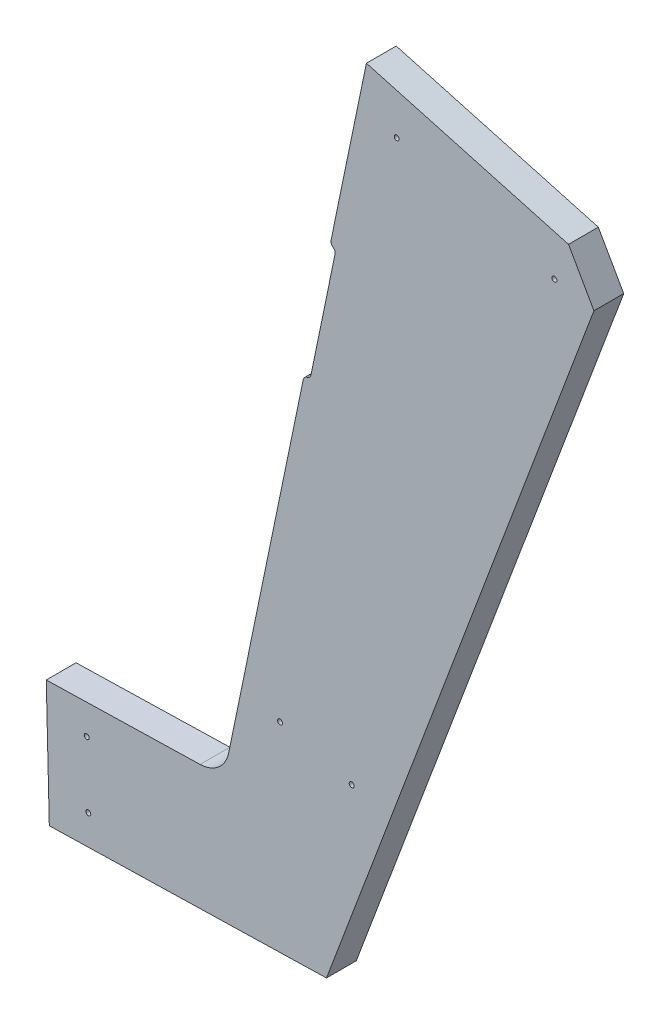
SolidWorks part; units mm, degrees
material "Beech"
ref_plane "Front Plane" through (0, 0, 0) normal (0, 0, 1) x (1, 0, 0)
ref_plane "Top Plane" through (0, 0, 0) normal (0, 1, 0) x (1, 0, 0)
ref_plane "Right Plane" through (0, 0, 0) normal (1, 0, 0) x (0, 0, -1)
sketch "Sketch1" plane through (0, 0, 0) normal (0, 0, 1) x (1, 0, 0)
  line L0 (-61.7531, -505.1337) -> (-59.8053, -584.9036)
  line L1 (-70.6552, -530.7587) -> (-61.1331, -530.5262) construction
  line L12 (272.1416, -96.993) -> (142.9339, -61.3062)
  line L13 (142.9339, -61.3062) -> (54.7807, -487.5464)
  line L14 (36.5905, -502.7325) -> (-61.7531, -505.1337)
  line L16 (-59.8053, -584.9036) -> (117.3871, -580.5771)
  line L17 (117.3871, -580.5771) -> (288.3946, -125.6501)
  line L37 (288.3946, -125.6501) -> (272.1416, -96.993)
  arc A0 (54.7807, -487.5464) -> (36.5905, -502.7325) centre (36.1255, -483.6882) cw
  dimension "D2" = 19.05
  dimension "D1" = 112
  dimension "D3" = 9.525
  dimension "D4" = 79.7937
  dimension "D5" = 435.6771
  dimension "D6" = 84.839
extrude "Boss-Extrude1" add sketch "Sketch1" along normal blind 19.05
hole_wizard "Hole2" positions "Sketch4" profile "Sketch5" legacy
sketch "Sketch4" plane through (295.8209, -105.8941, -19.05) normal (0, 0, -1) x (-0.3519, -0.9361, 0)
  line L0 (9.7688, 133.4475) -> (528.1685, 52.1167) construction
  line L5 (0.0093, 25.4) -> (517.3743, 25.4) construction
  line L8 (660.1216, 540.8653) -> (441.5979, 0) construction
  line L11 (698.7793, 525.2466) -> (486.5659, 0) construction
  line L15 (604.5365, 403.2872) -> (643.1942, 387.6685) construction
  line L17 (520.7568, 195.9254) -> (559.4145, 180.3066) construction
  line L19 (507.6737, 163.5435) -> (546.3314, 147.9247) construction
  point P17 (34.8618, 129.5107)
  point P19 (398.7112, 72.427)
  point P22 (25.4093, 25.4)
  point P24 (393.7093, 25.4)
  point P40 (604.5365, 403.2872)
  point P41 (643.1942, 387.6685)
  point P44 (520.7568, 195.9254)
  point P45 (559.4145, 180.3066)
  point P48 (507.6737, 163.5435)
  point P49 (546.3314, 147.9247)
sketch "Sketch5" plane through (-34.8779, -565.2393, -19.05) normal (1, 0, 0) x (0, 1, 0)
  line L0 (0, 0) -> (0, 40.64)
  line L1 (0, 40.64) -> (1.5875, 39.6861)
  line L2 (1.5875, 39.6861) -> (1.5875, 4.0177)
  line L3 (1.5875, 4.0177) -> (5.08, 0)
  line L4 (5.08, 0) -> (0, 0)
  line L5 (0, -14.3089) -> (0, 102.4216) construction
  line L6 (0, 40.64) -> (-1.5875, 39.6861) construction
  line L7 (-1.5875, 4.0177) -> (-5.08, 0) construction
  dimension "Diameter" = 3.175
  dimension "Depth" = 40.64
  dimension "C-Sink Diameter" = 10.16
  dimension "C-Sink Angle" = 82
  dimension "Drill Angle" = 118
sketch "Sketch6" plane through (149.23, -30.8631, 0) normal (-0.9793, 0.2025, 0) x (0, 0, 1)
  line L0 (19.05, -31.0873) -> (19.05, -466.3478) construction
  line L1 (19.05, -145.3873) -> (0, -145.3873)
  line L2 (19.05, -145.3873) -> (19.05, -227.9373)
  line L3 (19.05, -227.9373) -> (0, -227.9373)
  line L4 (0, -145.3873) -> (0, -227.9373)
  line L5 (0, -31.0873) -> (0, -466.3478) construction
  line L6 (19.05, -31.0873) -> (0, -31.0873) construction
  dimension "D1" = 114.3
  dimension "D2" = 82.55
extrude "Cut-Extrude1" cut sketch "Sketch6" against normal blind 3.81
fillet "Fillet1" radius 3.175 2 edges at (106.797, -254.8484, 9.525) (123.5158, -174.0091, 9.525)
fillet "Fillet2" radius 3.175 2 edges at (119.7847, -173.2375, 9.525) (103.0659, -254.0767, 9.525)
hole_wizard "15/64 (0.23438) Diameter Hole1" positions "Sketch7" profile "Sketch8" hole size "15/64" standard "ANSI Inch"
sketch "Sketch7" plane through (152.9611, -31.6348, 0) normal (-0.9793, 0.2025, 0) x (0, 0, 1)
  point P0 (9.525, -186.6623)
sketch "Sketch8" plane through (115.1564, -214.4287, 9.525) normal (0, 0, 1) x (-0.2025, -0.9793, 0)
  line L0 (0, 0) -> (0, 17.6635)
  line L1 (0, 17.6635) -> (2.9766, 15.875)
  line L2 (2.9766, 15.875) -> (2.9766, 0)
  line L5 (2.9766, 0) -> (0, 0)
  line L10 (0, 17.6635) -> (-2.9766, 15.875) construction
  line L11 (0, -6.35) -> (0, 107.95) construction
  dimension "Hole Dia." = 5.9533
  dimension "Hole Depth" = 15.875
  dimension "Drill Angle" = 118
